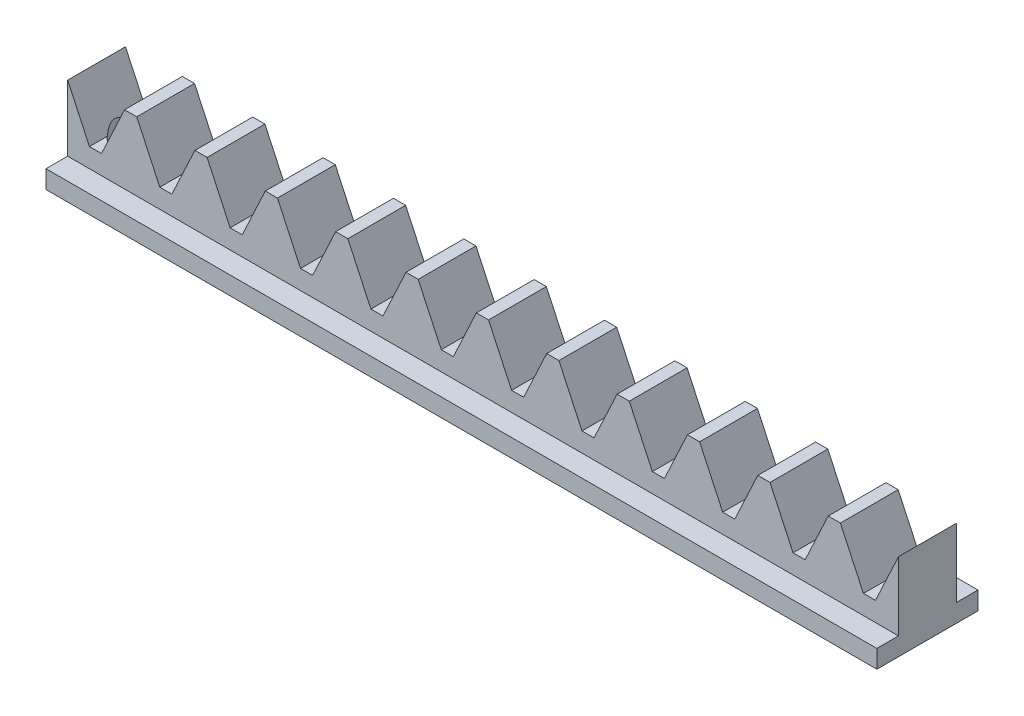
SolidWorks part; units mm, degrees
ref_plane "Front Plane" through (0, 0, 0) normal (0, 0, 1) x (1, 0, 0)
ref_plane "Top Plane" through (0, 0, 0) normal (0, 1, 0) x (1, 0, 0)
ref_plane "Right Plane" through (0, 0, 0) normal (1, 0, 0) x (0, 0, -1)
sketch "Sketch1" plane through (0, 0, 0) normal (0, 0, 1) x (1, 0, 0)
  circle A0 centre (0, 0) radius 32.55
  circle A1 centre (0, 0) radius 35.65
  circle A2 centre (0, 0) radius 28.675
  dimension "D1" = 65.1
  dimension "D2" = 71.3
  dimension "D3" = 6.975
sketch "Sketch9" plane through (0, 0, 0) normal (0, 0, 1) x (1, 0, 0)
  line L0 (49.45, 6) -> (52.64, -0.841)
  line L1 (-57.5, 6) -> (57.5, 6)
  line L2 (-57.5, 6) -> (-57.5, -6)
  line L3 (-57.5, -6) -> (57.5, -6)
  line L4 (57.5, 6) -> (57.5, -6)
  line L5 (-57.5, 6) -> (57.5, -6) construction
  line L6 (-57.5, -6) -> (57.5, 6) construction
  line L7 (52.64, -0.841) -> (54.31, -0.841)
  line L8 (57.5, 6) -> (54.31, -0.841)
  line L9 (53.475, -0.841) -> (53.475, 7.325) construction
  line L10 (51.045, 2.5795) -> (55.905, 2.5795) construction
  point P0 (0, 0)
  dimension "D1" = 115
  dimension "D2" = 12
  dimension "D3" = 3.4205
  dimension "D4" = 3.4205
  dimension "D5" = 25
  dimension "D6" = 4.86
  dimension "D7" = 2.43
extrude "Boss-Extrude4" add sketch "Sketch9" along normal mid plane 8 contours L8 L1 L0 L7 | L1 L8 L7 L0 L2 L3 L4 region at (53.475, 3.3279, 0) region at (-1.3201, -0.0822, 0)
extrude "Cut-Extrude7" cut sketch "Sketch9<4>" against normal through all both and the other way through all contours L8 L1 L0 L7 region at (53.475, 3.3279, 0)
sketch "Sketch9<4>" plane through (0, 0, 0) normal (0, 0, 1) x (1, 0, 0) same geometry as "Sketch9"
pattern_linear "LPattern2" count 13 spacing 9.7389 along (-1, 0, 0) of "Cut-Extrude7"
sketch "Sketch10" plane through (-57.5, 0, 0) normal (-1, 0, 0) x (0, 0, 1)
  line L0 (4, 5.6185) -> (4, -6) construction
  line L1 (7, -6) -> (-7, -6)
  line L2 (7, -6) -> (7, -3.5)
  line L3 (7, -3.5) -> (-7, -3.5)
  line L4 (-7, -6) -> (-7, -3.5)
  dimension "D1" = 2.5
  dimension "D2" = 14
  dimension "D3" = 3
extrude "Boss-Extrude5" add sketch "Sketch10" against normal up to surface (115 mm away) up to face at (57.5, 0, 0)
sketch "Sketch11" plane through (0, -6, 0) normal (0, -1, 0) x (1, 0, 0)
  line L0 (-57.5, 7) -> (-57.5, -7) construction
  circle A0 centre (-52.5, 0) radius 2.5
  dimension "D1" = 5
extrude "Cut-Extrude8" cut sketch "Sketch11" against normal through all
equation "\"Module\"= 3.1mm"
equation "\"Number of Teeth\"= 21"
equation "\"D1@Sketch1\"=\"Module\" * \"Number of Teeth\""
equation "\"D2@Sketch1\"=(\"Number of Teeth\" + 2) * \"Module\""
equation "\"D3@Sketch1\"=\"Module\" * if(\"Module\"=>1.25,2.25,2.4)"
equation "\"D5@Sketch4\"= 180 / \"Number of Teeth\""
equation "\"D1@Fillet1\"= .3 * \"Module\""
equation "\"D1@CirPattern1\"= \"Number of Teeth\""
